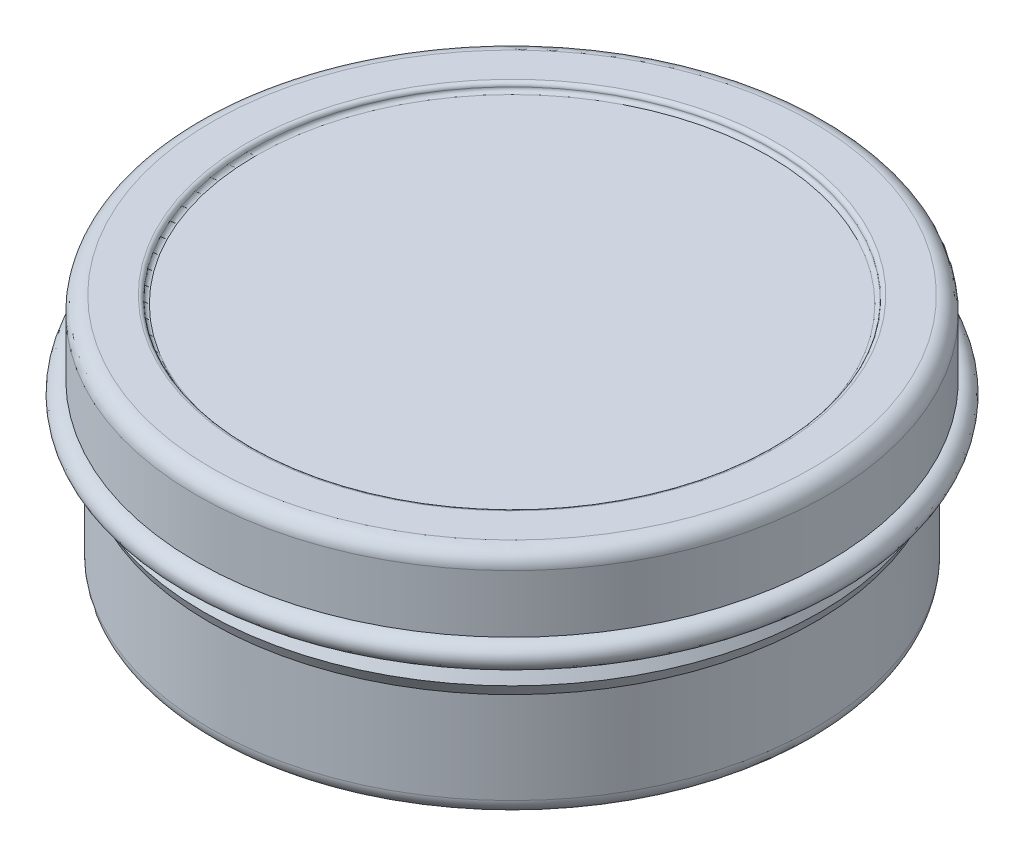
SolidWorks part; units mm, degrees
ref_plane "Front Plane" through (0, 0, 0) normal (0, 0, 1) x (1, 0, 0)
ref_plane "Top Plane" through (0, 0, 0) normal (0, 1, 0) x (1, 0, 0)
ref_plane "Right Plane" through (0, 0, 0) normal (1, 0, 0) x (0, 0, -1)
ref_axis "Axis1" through (-33.0333, 0, 0) along (1, 0, 0)
ref_axis "Axis2" through (0, 24.5224, 0) along (0, -1, 0)
ref_axis "Axis3" through (0, 0, -30.7663) along (0, 0, 1)
sketch "Sketch1" plane through (0, 0, 0) normal (0, 0, 1) x (1, 0, 0)
  line L22 (0, 0) -> (-19.45, 0)
  line L28 (-19.45, 0) -> (-19.45, 6.9)
  line L29 (-19.45, 6.9) -> (-19.825, 7.6575)
  line L30 (-19.825, 7.6575) -> (-19.45, 8.4151)
  line L31 (-19.45, 8.4151) -> (-19.45, 9.1)
  line L32 (-19.45, 9.1) -> (-20.3, 9.1)
  line L33 (-20.3, 10.7) -> (-20.3, 15.41)
  line L34 (-20.3, 15.41) -> (0, 15.41)
  line L35 (0, 15.41) -> (0, 0)
  line L36 (-21.2, 9.9) -> (-20.3, 9.9) construction
  line L37 (-19.45, 8.4151) -> (-19.45, 6.9) construction
  line L38 (-19.825, 7.6575) -> (-19.45, 7.6575) construction
  ellipse E0 centre (-20.3, 9.9) end of major axis (-21.2, 9.9) minor radius 0.8 (-20.3, 10.7) -> (-20.3, 9.1) ccw
  point P10 (-19.825, 7.6575)
  dimension "D2" = 20.3
  dimension "D1" = 19.45
  dimension "D3" = 15.41
  dimension "D4" = 6.9
  dimension "D5" = 1.6
  dimension "D6" = 4.71
  dimension "D7" = 21.2
  dimension "D8" = 19.825
revolve "Revolve1" add sketch "Sketch1" angle 360 about axis through (0, 24.5224, 0) along (0, -1, 0)
sketch "Sketch2" plane through (0, 15.41, 0) normal (0, 1, 0) x (1, 0, 0)
  circle A0 centre (0, 0) radius 16.75
  dimension "D1" = 33.5
extrude "Cut-Extrude1" cut sketch "Sketch2" against normal blind 0.5
fillet "Fillet1" radius 1 2 edges at (0, 15.41, 20.3) (0, 0, 19.45)
fillet "Fillet2" radius 0.25 2 edges at (0, 14.91, 16.75) (0, 15.41, 16.75)
